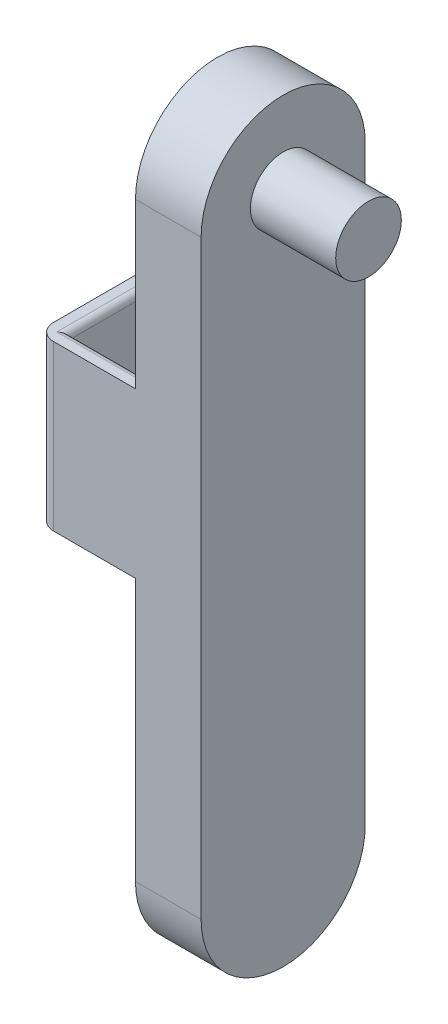
SolidWorks part; units mm, degrees
ref_plane "Front Plane" through (0, 0, 0) normal (0, 0, 1) x (1, 0, 0)
ref_plane "Top Plane" through (0, 0, 0) normal (0, 1, 0) x (1, 0, 0)
ref_plane "Right Plane" through (0, 0, 0) normal (1, 0, 0) x (0, 0, -1)
sketch "Sketch1" plane through (0, 0, 0) normal (1, 0, 0) x (0, 0, -1)
  line L0 (-17.2349, 15.5155) -> (-17.2349, -2.4845)
  line L1 (-12.2349, 15.5155) -> (-12.2349, -2.4845)
  arc A0 (-17.2349, 15.5155) -> (-12.2349, 15.5155) centre (-14.7349, 15.5155) cw
  arc A1 (-12.2349, -2.4845) -> (-17.2349, -2.4845) centre (-14.7349, -2.4845) cw
  dimension "D1" = 18
  dimension "D2" = 5
extrude "Boss-Extrude1" add sketch "Sketch1" along normal blind 2
sketch "Sketch2" plane through (2, 0, 0) normal (1, 0, 0) x (0, 0, -1)
  circle A0 centre (-14.7349, 15.5155) radius 1
  dimension "D1" = 2
extrude "Boss-Extrude2" add sketch "Sketch2" along normal blind 2.6
sketch "Sketch3" plane through (0, 0, 12.2349) normal (0, 0, -1) x (-1, 0, 0)
  line L0 (0, -2.4845) -> (0, 15.5155) construction
  line L1 (0, 10.5155) -> (3, 10.5155)
  line L2 (0, 10.5155) -> (0, 5.5155)
  line L3 (0, 5.5155) -> (3, 5.5155)
  line L4 (3, 10.5155) -> (3, 5.5155)
  line L5 (-2, 15.5155) -> (0, 15.5155) construction
  dimension "D1" = 3
  dimension "D2" = 5
  dimension "D3" = 5
extrude "Boss-Extrude3" add sketch "Sketch3" against normal up to surface (5 mm away) up to face at (1, 6.5155, 17.2349)
sketch "Sketch4" plane through (0, 10.5155, 0) normal (0, 1, 0) x (1, 0, 0)
  line L0 (0, -17.2349) -> (-3, -17.2349) construction
  line L1 (-0.5, -16.7349) -> (-2.5, -16.7349)
  line L2 (-0.5, -16.7349) -> (-0.5, -12.7349)
  line L3 (-0.5, -12.7349) -> (-2.5, -12.7349)
  line L4 (-2.5, -16.7349) -> (-2.5, -12.7349)
  line L5 (-3, -12.2349) -> (0, -12.2349) construction
  line L6 (-3, -17.2349) -> (-3, -12.2349) construction
  line L7 (0, -17.2349) -> (0, -12.2349) construction
  dimension "D1" = 0.5
  dimension "D2" = 0.5
  dimension "D3" = 0.5
  dimension "D4" = 0.5
extrude "Cut-Extrude1" cut sketch "Sketch4" against normal through all
fillet "Fillet1" radius 0.5 2 edges at (-3, 8.0155, 17.2349) (-3, 8.0155, 12.2349)
fillet "Fillet2" radius 0.2 8 edges at (-1.5, 5.5155, 12.7349) (-2.5, 5.5155, 14.7349) (-1.5, 5.5155, 16.7349) (-0.5, 5.5155, 14.7349) (-2.5, 10.5155, 14.7349) (-1.5, 10.5155, 16.7349) (-1.5, 10.5155, 12.7349) (-0.5, 10.5155, 14.7349)
